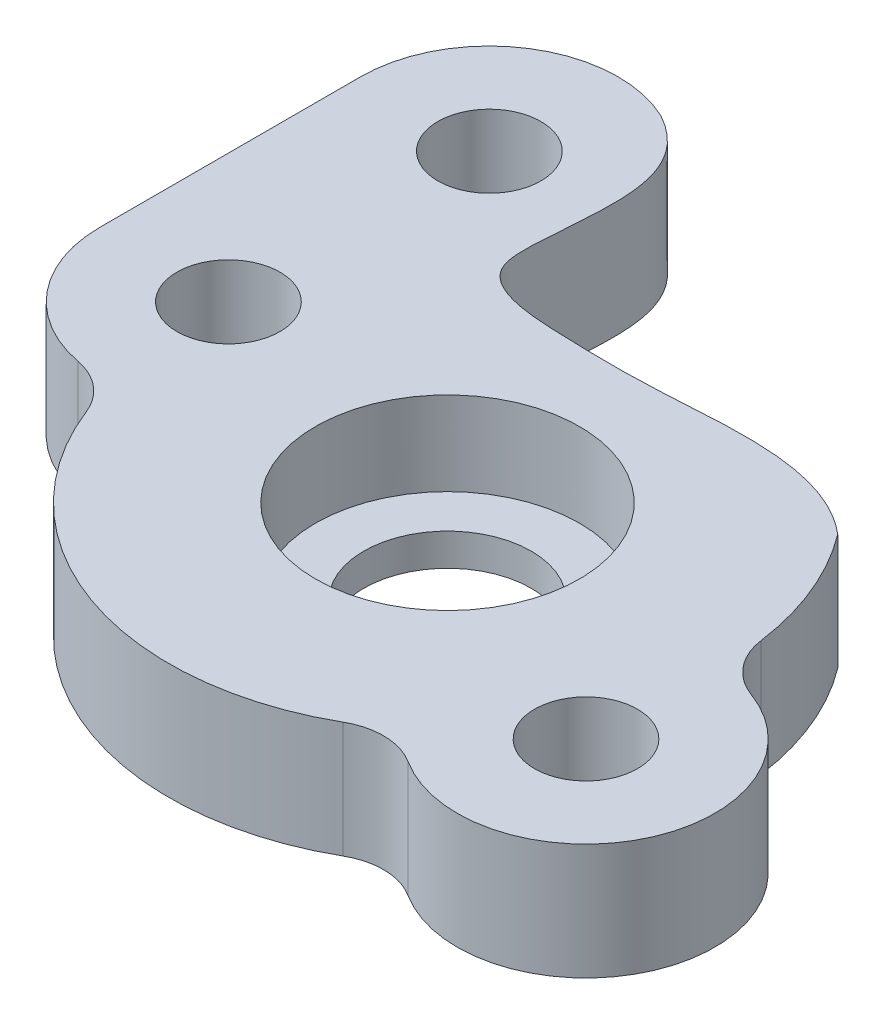
SolidWorks part; units mm, degrees
ref_plane "前视基准面" through (0, 0, 0) normal (0, 0, 1) x (1, 0, 0)
ref_plane "上视基准面" through (0, 0, 0) normal (0, 1, 0) x (1, 0, 0)
ref_plane "右视基准面" through (0, 0, 0) normal (1, 0, 0) x (0, 0, -1)
other "Configuration Table"
sketch "草图1" plane through (0, 0, 0) normal (0, 1, 0) x (1, 0, 0)
  line L1 (0, 0) -> (30, 0)
  line L2 (0, 0) -> (0, 30)
  line L3 (0, 30) -> (30, 30)
  line L4 (30, 0) -> (30, 30)
  dimension "D1" = 30
  dimension "D2" = 30
extrude "凸台-拉伸1" add sketch "草图1" along normal blind 3.6
sketch "草图2" plane through (0, 3.6, 0) normal (0, 1, 0) x (1, 0, 0)
  line L0 (0, 0) -> (30, 0) construction
  line L1 (0, 30) -> (0, 0) construction
  circle A0 centre (21.35, 4.45) radius 1.6
  circle A1 centre (4.05, 10.65) radius 1.6
  circle A2 centre (12.85, 8.65) radius 4.1
  dimension "D1" = 3.2
  dimension "D2" = 3.2
  dimension "D3" = 8.2
  dimension "D4" = 10.65
  dimension "D5" = 4.05
  dimension "D6" = 17.3
  dimension "D7" = 6.2
  dimension "D8" = 8.5
  dimension "D9" = 4.2
  dimension "D10" = 2
  dimension "D11" = 8.8
extrude "切除-拉伸1" cut sketch "草图2" against normal blind 3.6
sketch "草图3" plane through (0, 3.6, 0) normal (0, 1, 0) x (1, 0, 0)
  circle A0 centre (4.05, 18.75) radius 1.6
  circle A1 centre (4.05, 10.65) radius 1.6 construction
  dimension "D1" = 3.2
  dimension "D2" = 8.1
  dimension "D3" = 0
extrude "切除-拉伸2" cut sketch "草图3" against normal blind 3.6
sketch "草图4" plane through (0, 0, 0) normal (0, -1, 0) x (-1, 0, 0)
  circle A3 centre (-12.85, 8.65) radius 2.6
  circle A4 centre (-12.85, 8.65) radius 4.1
  circle A5 centre (-12.85, 8.65) radius 4.1
  dimension "D1" = 0
  dimension "D2" = 5.2
extrude "凸台-拉伸2" add sketch "草图4" against normal blind 1
sketch "草图5" plane through (0, 0, 0) normal (0, -1, 0) x (1, 0, 0)
  line L0 (0.05, -10.65) -> (0.05, -18.75)
  arc A0 (19.7558, -13.8588) -> (21.4976, -8.4473) centre (12.85, -8.65) ccw
  arc A1 (4.4301, -6.6681) -> (0.05, -10.65) centre (4.05, -10.65) ccw
  arc A2 (21.4976, -8.4473) -> (18.2646, -1.9043) centre (21.35, -4.45) ccw
  arc A3 (0.05, -18.75) -> (5.7532, -22.3693) centre (4.05, -18.75) ccw
  arc A4 (18.2646, -1.9043) -> (4.4301, -6.6681) centre (12.85, -8.65) ccw
  spline S0 degree 3 poles (5.7532, -22.3693) (7.856, -21.225) (7.2623, -18.7324) (7.2146, -15.0426) (10.3251, -14.9119) (14.194, -14.8693) (17.852, -15.4712) (19.7558, -13.8588) knots 0 0 0 0 0.297903 0.356444 0.512121 0.640128 1 1 1 1
  point P5 (7.082, -20.9876)
  point P12 (0, 0)
  point P14 (18.2646, -14.6975)
  point P16 (10.3137, -14.9283)
  point P18 (12.85, -14.9283)
  dimension "D1" = 17.3
  dimension "D2" = 8
  dimension "D3" = 8
  dimension "D4" = 8
extrude "切除-拉伸3" cut sketch "草图5" against normal through all flip side to cut
fillet "圆角1" radius 2 3 edges at (21.4976, 1.8, -8.4473) (4.4301, 1.8, -6.6681) (18.2646, 1.8, -1.9043)
equation "\"D1@草图5\"=8.65*2"
